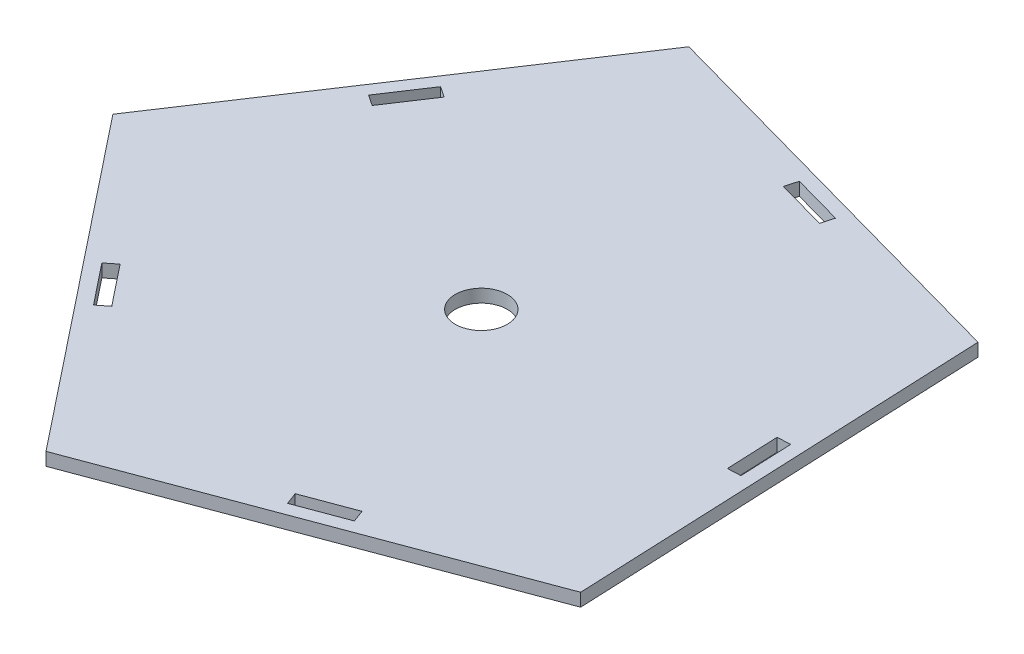
SolidWorks part; units mm, degrees
ref_plane "Front Plane" through (0, 0, 0) normal (0, 0, 1) x (1, 0, 0)
ref_plane "Top Plane" through (0, 0, 0) normal (0, 1, 0) x (1, 0, 0)
ref_plane "Right Plane" through (0, 0, 0) normal (1, 0, 0) x (0, 0, -1)
sketch "Sketch1" plane through (0, 0, 0) normal (0, 1, 0) x (1, 0, 0)
  line L1 (-20.8753, -32.8264) -> (-29.6171, 170.1854)
  line L2 (-29.6171, 170.1854) -> (-225.3943, 224.6055)
  line L3 (-225.3943, 224.6055) -> (-337.6493, 55.2271)
  line L4 (-337.6493, 55.2271) -> (-211.2496, -103.8746)
  line L5 (-211.2496, -103.8746) -> (-20.8753, -32.8264)
  circle A0 centre (-164.9571, 62.6634) radius 139.8404 construction
  dimension "D1" = 203.2
extrude "Boss-Extrude1" add sketch "Sketch1" along normal blind 6.35
sketch "Sketch2" plane through (0, 6.35, 0) normal (0, 1, 0) x (1, 0, 0)
  line L0 (-211.2496, -103.8746) -> (-20.8753, -32.8264) construction
  line L1 (-132.4014, -60.8926) -> (-108.6046, -52.0116)
  line L2 (-132.4014, -60.8926) -> (-130.1811, -66.8418)
  line L3 (-130.1811, -66.8418) -> (-106.3843, -57.9608)
  line L4 (-108.6046, -52.0116) -> (-106.3843, -57.9608)
  line L5 (-337.6493, 55.2271) -> (-211.2496, -103.8746) construction
  line L6 (-277.3775, -10.4299) -> (-261.5776, -30.3176)
  line L7 (-277.3775, -10.4299) -> (-272.4056, -6.4799)
  line L8 (-272.4056, -6.4799) -> (-256.6056, -26.3676)
  line L9 (-261.5776, -30.3176) -> (-256.6056, -26.3676)
  line L10 (-225.3943, 224.6055) -> (-337.6493, 55.2271) construction
  line L11 (-283.2447, 125.8222) -> (-277.9516, 122.3143)
  line L12 (-283.2447, 125.8222) -> (-269.2128, 146.9945)
  line L13 (-269.2128, 146.9945) -> (-263.9197, 143.4866)
  line L14 (-277.9516, 122.3143) -> (-263.9197, 143.4866)
  line L15 (-29.6171, 170.1854) -> (-225.3943, 224.6055) construction
  line L16 (-141.4424, 194.6787) -> (-116.9703, 187.8762)
  line L17 (-141.4424, 194.6787) -> (-143.143, 188.5607)
  line L18 (-143.143, 188.5607) -> (-118.6709, 181.7582)
  line L19 (-116.9703, 187.8762) -> (-118.6709, 181.7582)
  line L20 (-20.8753, -32.8264) -> (-29.6171, 170.1854) construction
  line L21 (-38.4808, 80.8214) -> (-32.1367, 81.0946)
  line L22 (-38.4808, 80.8214) -> (-37.3881, 55.4449)
  line L23 (-37.3881, 55.4449) -> (-31.0439, 55.7181)
  line L24 (-32.1367, 81.0946) -> (-31.0439, 55.7181)
  point P27 (-117.8206, 184.8172)
  dimension "D1" = 6.35
  dimension "D2" = 25.4
  dimension "D3" = 6.35
  dimension "D4" = 88.9
  dimension "D5" = 25.4
  dimension "D6" = 6.35
  dimension "D7" = 6.35
  dimension "D8" = 88.9
  dimension "D9" = 25.4
  dimension "D10" = 6.35
  dimension "D11" = 6.35
  dimension "D12" = 88.9
  dimension "D13" = 6.35
  dimension "D14" = 25.4
  dimension "D15" = 6.35
  dimension "D16" = 88.9
  dimension "D17" = 6.35
  dimension "D18" = 25.4
  dimension "D19" = 6.35
  dimension "D20" = 88.9
extrude "Cut-Extrude1" cut sketch "Sketch2" against normal through all
sketch "Sketch3" plane through (0, 6.35, 0) normal (0, 1, 0) x (1, 0, 0)
  line L0 (-225.3943, 224.6055) -> (-116.0624, -68.3505) construction
  line L1 (-211.2496, -103.8746) -> (-20.8753, -32.8264) construction
  line L2 (-337.6493, 55.2271) -> (-25.2462, 68.6795) construction
  line L4 (-29.6171, 170.1854) -> (-274.4495, -24.3237) construction
  line L5 (-337.6493, 55.2271) -> (-211.2496, -103.8746) construction
  line L6 (-20.8753, -32.8264) -> (-29.6171, 170.1854) construction
  circle A0 centre (-164.9571, 62.6634) radius 12.7
  point P4 (0, 0)
  point P18 (0, 0)
  point P19 (0, 0)
  point P21 (-164.9571, 62.6634)
  point P22 (0, 0)
  point P23 (-164.9571, 62.6634)
extrude "Cut-Extrude2" cut sketch "Sketch3" against normal through all
